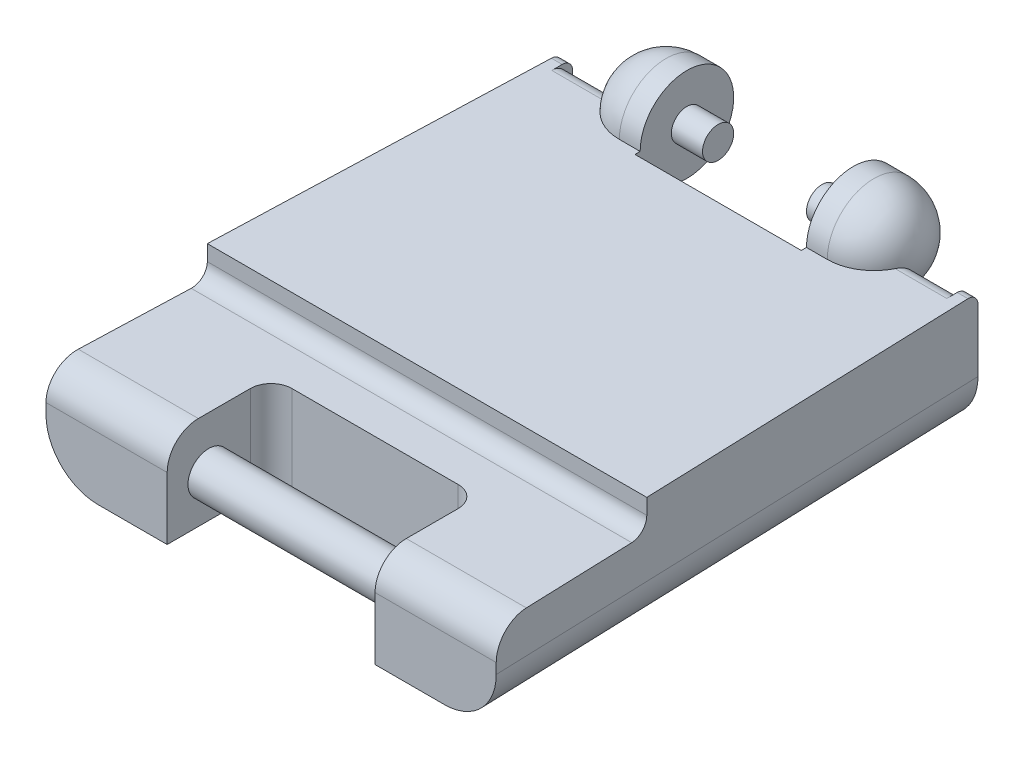
SolidWorks part; units mm, degrees
material "PF"
ref_plane "Спереди" through (0, 0, 0) normal (0, 0, 1) x (1, 0, 0)
ref_plane "Сверху" through (0, 0, 0) normal (0, 1, 0) x (1, 0, 0)
ref_plane "Справа" through (0, 0, 0) normal (1, 0, 0) x (0, 0, -1)
sketch "Эскиз1" plane through (0, 0, 0) normal (1, 0, 0) x (0, 0, -1)
  line L0 (-72.1628, 0) -> (7.6884, 0) construction
  line L1 (0, 6.6767) -> (0, -19.2209) construction
  line L3 (-58, 0) -> (0, 0)
  line L4 (-58, 0) -> (-58, -12)
  line L5 (-58, -12) -> (0, -12)
  line L6 (0, 0) -> (0, -12)
  dimension "D1" = 58
  dimension "D2" = 12
extrude "Бобышка-Вытянуть1" add sketch "Эскиз1" along normal mid plane 44
sketch "Эскиз3" plane through (0, 0, 0) normal (0, 1, 0) x (1, 0, 0)
  line L0 (0, 3.25) -> (0, -59.3375) construction
  line L1 (-22, -58) -> (-20, 0) construction
  line L2 (22, 0) -> (-22, 0) construction
  line L3 (-20, 0) -> (-22, 0)
  line L4 (-22, 0) -> (-22, -58)
  line L5 (-20, 0) -> (-21.6552, -48)
  line L6 (-21.6552, -48) -> (-10, -48)
  line L7 (-10, -48) -> (-10, -40)
  line L8 (-8, -38) -> (8, -38)
  line L9 (10, -48) -> (10, -40)
  line L10 (21.6552, -48) -> (10, -48)
  line L11 (20, 0) -> (21.6552, -48)
  line L12 (22, 0) -> (22, -58)
  line L13 (20, 0) -> (22, 0)
  line L14 (-22, -58) -> (22, -58)
  arc A0 (-10, -40) -> (-8, -38) centre (-8, -40) cw
  arc A1 (10, -40) -> (8, -38) centre (8, -40) ccw
  point P17 (0, -38)
  dimension "D5" = 2
  dimension "D1" = 20
  dimension "D2" = 48
  dimension "D3" = 10
  dimension "D4" = 10
extrude "Вырез-Вытянуть2" cut sketch "Эскиз3" against normal up to surface (12 mm away) up to face at (0, -12, 29)
fillet "Скругление2" radius 5 2 edges at (-20.8276, -12, 24) (20.8276, -12, 24)
sketch "Эскиз4" plane through (0, 0, 0) normal (1, 0, 0) x (0, 0, -1)
  line L0 (-50.6524, 0) -> (3.6956, 0) construction
  line L1 (-33, 0) -> (-33, -1.5)
  line L2 (-34.5, -3) -> (-45, -3)
  line L3 (-48, -7) -> (-48, 0) construction
  line L4 (-48, -6) -> (-48, 0)
  line L5 (0, 0) -> (-48, 0) construction
  line L6 (-48, 0) -> (-33, 0)
  line L7 (0, 4.2051) -> (0, -15.0267) construction
  arc A0 (-34.5, -3) -> (-33, -1.5) centre (-34.5, -1.5) ccw
  arc A1 (-48, -6) -> (-45, -3) centre (-45, -6) cw
  point P14 (-48, -3)
  dimension "D3" = 1.5
  dimension "D4" = 3
  dimension "D1" = 3
  dimension "D2" = 15
extrude "Вырез-Вытянуть3" cut sketch "Эскиз4" against normal mid plane 44
sketch "Эскиз5" plane through (0, 0, 0) normal (0, 0, -1) x (-1, 0, 0)
  line L0 (0, 3.1244) -> (0, -14.001) construction
  line L1 (19, 0) -> (-19, 0)
  line L3 (-19, -7) -> (-19, 0)
  line L4 (-19, -7) -> (-19, 0)
  line L8 (19, -7) -> (19, 0)
  line L11 (-14.997, -11) -> (14.997, -11)
  spline S0 degree 3 poles (1089.1122, -2788.9883) (139.4551, 104.8109) (-27.2466, 12.1017) (-18.4949, -9.0142) (-18.1983, -9.4579) (-17.4573, -10.1985) (-17.0132, -10.495) (4.1053, -19.2374) (96.884, 147.1071) (-2796.9276, 1097.441) knots -10.413735 -10.413735 -10.413735 -10.413735 0.25 0.25 0.5 0.5 0.75 0.75 11.405152 11.405152 11.405152 11.405152 only from (-19, -7) to (-14.997, -11)
  spline S1 degree 3 poles (-19, -7) (-19, -7.5235) (-18.8958, -8.0468) (-18.4949, -9.0142) (-18.1983, -9.4579) (-17.4573, -10.1985) (-17.0132, -10.495) (-16.045, -10.8959) (-15.5211, -11) (-14.997, -11) knots 0 0 0 0 0.25 0.25 0.5 0.5 0.75 0.75 1 1 1 1
  spline S2 degree 3 poles (19, -7) (19, -7.5235) (18.8958, -8.0468) (18.4949, -9.0142) (18.1983, -9.4579) (17.4573, -10.1985) (17.0132, -10.495) (16.045, -10.8959) (15.5211, -11) (14.997, -11) knots 0 0 0 0 0.25 0.25 0.5 0.5 0.75 0.75 1 1 1 1
  dimension "D1" = 1
  dimension "D2" = 1
extrude "Вырез-Вытянуть4" cut sketch "Эскиз5" against normal blind 0.5
fillet "Скругление4" radius 1.5 1 edges at (0, 0, 0.5)
fillet "Скругление5" radius 1 2 edges at (-19.5, 0, 0) (19.5, 0, 0)
sketch "Эскиз6" plane through (0, 0, 0) normal (1, 0, 0) x (0, 0, -1)
  line L0 (-36.3479, 0) -> (7.9474, 0) construction
  line L1 (0, 10.9473) -> (0, -15.1721) construction
  circle A0 centre (0, 0) radius 5
  dimension "D1" = 10
extrude "Вырез-Вытянуть5" cut sketch "Эскиз6" against normal mid plane 16
sketch "Эскиз7" plane through (0, 0, 0) normal (0, 0, -1) x (-1, 0, 0)
  line L0 (0, 4.2175) -> (0, -15.9746) construction
  line L1 (-23.5019, 0) -> (28.2387, 0) construction
  line L2 (-14.5, 0) -> (-5, 0)
  line L3 (-8, -1.5) -> (-8, -4.5)
  line L4 (-8, -4.9749) -> (-8, 0) construction
  line L5 (-8, -4.5) -> (-10, -4.5)
  line L6 (-8, -1.5) -> (-5, -1.5)
  line L7 (-5, -1.5) -> (-5, 0)
  line L8 (8, -4.5) -> (10, -4.5)
  line L9 (8, -1.5) -> (8, -4.5)
  line L10 (8, -1.5) -> (5, -1.5)
  line L11 (5, -1.5) -> (5, 0)
  line L12 (14.5, 0) -> (5, 0)
  arc A0 (-10, -4.5) -> (-14.5, 0) centre (-10, 0) cw
  arc A1 (10, -4.5) -> (14.5, 0) centre (10, 0) ccw
  dimension "D1" = 4.5
  dimension "D2" = 2
  dimension "D3" = 3
  dimension "D4" = 1.5
revolve "Повернуть1" add sketch "Эскиз7" angle 360 about L1
sketch "Эскиз8" plane through (0, 0, 0) normal (1, 0, 0) x (0, 0, -1)
  line L0 (-50.6434, 0) -> (9.2782, 0) construction
  line L1 (-48, -7) -> (-48, -12) construction
  line L2 (0, -12) -> (-48, -12) construction
  circle A0 centre (-44, -8) radius 2
  dimension "D1" = 4
  dimension "D2" = 4
  dimension "D3" = 4
extrude "Бобышка-Вытянуть2" add sketch "Эскиз8" along normal mid plane 20
sketch "Эскиз9" plane through (0, -12, 0) normal (0, -1, 0) x (1, 0, 0)
  line L0 (0, -5.6861) -> (0, 49.1861) construction
  line L1 (9.6525, 2) -> (-9.6525, 2)
  line L2 (-14.1498, 6.3449) -> (-14.9429, 29.3449)
  line L3 (-10.4456, 34) -> (10.4456, 34)
  line L4 (-16.6522, 48) -> (-14.997, 0) construction
  line L5 (14.997, 0) -> (-14.997, 0) construction
  line L6 (14.1498, 6.3449) -> (14.9429, 29.3449)
  arc A0 (-9.6525, 2) -> (-14.1498, 6.3449) centre (-9.6525, 6.5) cw
  arc A1 (-14.9429, 29.3449) -> (-10.4456, 34) centre (-10.4456, 29.5) cw
  arc A2 (9.6525, 2) -> (14.1498, 6.3449) centre (9.6525, 6.5) ccw
  arc A3 (14.9429, 29.3449) -> (10.4456, 34) centre (10.4456, 29.5) ccw
  point P13 (-14, 2)
  point P17 (0, 2)
  point P22 (0, 34)
  dimension "D4" = 4.5
  dimension "D1" = 2
  dimension "D2" = 32
  dimension "D3" = 14
extrude "Вырез-Вытянуть7" cut sketch "Эскиз9" against normal blind 0.5
sketch "Эскиз10" plane through (0, -11.5, 0) normal (0, -1, 0) x (1, 0, 0)
  line L0 (0, -1.9938) -> (0, 39.9965) construction
  line L5 (10.4456, 34) -> (-10.4456, 34) construction
  line L9 (-9.6525, 2.5) -> (9.6525, 2.5)
  line L10 (13.6501, 6.3622) -> (14.4432, 29.3622)
  line L11 (10.4456, 33.5) -> (-10.4456, 33.5)
  line L12 (-14.4432, 29.3622) -> (-13.6501, 6.3622)
  line L13 (-9.6525, 2.5) -> (9.6525, 2.5)
  line L14 (13.6501, 6.3622) -> (14.4432, 29.3622)
  line L15 (10.4456, 33.5) -> (-10.4456, 33.5)
  line L16 (-14.4432, 29.3622) -> (-13.6501, 6.3622)
  circle A4 centre (0, 26) radius 5
  arc A8 (-13.6501, 6.3622) -> (-9.6525, 2.5) centre (-9.6525, 6.5) ccw
  arc A9 (9.6525, 2.5) -> (13.6501, 6.3622) centre (9.6525, 6.5) ccw
  arc A10 (14.4432, 29.3622) -> (10.4456, 33.5) centre (10.4456, 29.5) ccw
  arc A11 (-10.4456, 33.5) -> (-14.4432, 29.3622) centre (-10.4456, 29.5) ccw
  arc A12 (-13.6501, 6.3622) -> (-9.6525, 2.5) centre (-9.6525, 6.5) ccw
  arc A13 (9.6525, 2.5) -> (13.6501, 6.3622) centre (9.6525, 6.5) ccw
  arc A14 (14.4432, 29.3622) -> (10.4456, 33.5) centre (10.4456, 29.5) ccw
  arc A15 (-10.4456, 33.5) -> (-14.4432, 29.3622) centre (-10.4456, 29.5) ccw
  dimension "D3" = 10
  dimension "D2" = 8
  dimension "D1" = 0.5
extrude "Бобышка-Вытянуть3" add sketch "Эскиз10" along normal blind 1
sketch "Эскиз11" plane through (0, -11.5, 0) normal (0, -1, 0) x (1, 0, 0)
  circle A2 centre (0, 26) radius 4.5
  circle A3 centre (0, 26) radius 4.5
  dimension "D1" = 0.5
extrude "Бобышка-Вытянуть4" add sketch "Эскиз11" along normal blind 1
sketch "Эскиз12" plane through (0, -12.5, 0) normal (0, -1, 0) x (1, 0, 0)
  circle A0 centre (0, 26) radius 3
  dimension "D1" = 6
extrude "Вырез-Вытянуть8" cut sketch "Эскиз12" against normal blind 12
sketch "Эскиз13" plane through (0, -0.5, 0) normal (0, -1, 0) x (1, 0, 0)
  circle A2 centre (0, 26) radius 4
  circle A3 centre (0, 26) radius 4
  dimension "D1" = 1
extrude "Вырез-Вытянуть9" cut sketch "Эскиз13" along normal blind 2
sketch "Эскиз14" plane through (0, -12.5, 0) normal (0, -1, 0) x (1, 0, 0)
  circle A2 centre (0, 26) radius 3
  circle A3 centre (0, 26) radius 3
  dimension "D1" = 0
curve "Спираль1" pitch 1 height 10 turns 10
ref_plane "Плоскость1" through (0, 0, 26) normal (0, 0, -1) x (-1, 0, 0)
sketch "Эскиз15" plane through (0, 0, 26) normal (0, 0, -1) x (-1, 0, 0)
  line L1 (0, 3.5534) -> (0, -15.3353) construction
  line L2 (3, -10.1485) -> (3, -14.8515) construction
  line L3 (1.3096, -12.5) -> (4.6308, -12.5) construction
  line L8 (22.3616, 0) -> (-15.091, 0) construction
  line L9 (21.1379, 0) -> (-21.1379, 0) construction
  line L10 (3, -12.95) -> (4, -12.5)
  line L11 (3, -12.05) -> (4, -12.5)
  line L12 (3, -12.95) -> (3, -12.05)
  dimension "D1" = 3
  dimension "D2" = 12.5
  dimension "D3" = 0.45
  dimension "D4" = 1
sweep "Вырез-По траектории3" cut profiles "Эскиз15" path "Спираль1" align with end faces yes
